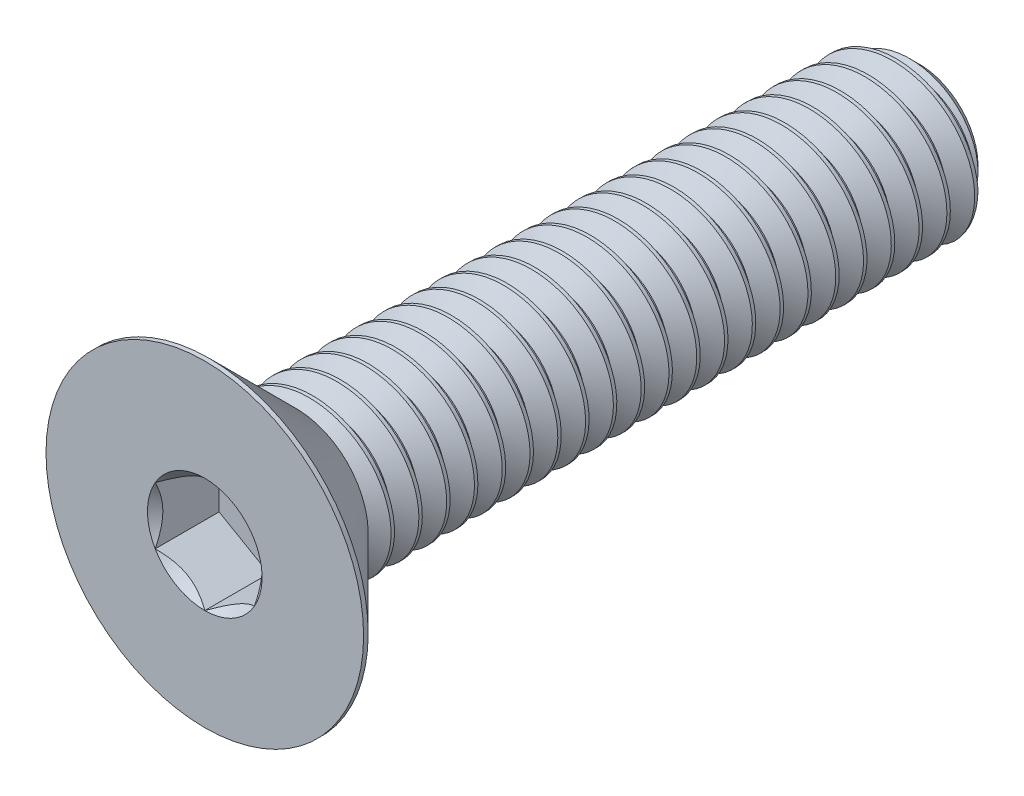
SolidWorks part; units mm, degrees
ref_plane "Front" through (0, 0, 0) normal (0, 0, 1) x (1, 0, 0)
ref_plane "Top" through (0, 0, 0) normal (0, 1, 0) x (1, 0, 0)
ref_plane "Right" through (0, 0, 0) normal (1, 0, 0) x (0, 0, -1)
sketch "Sketch11" plane through (0, 0, 0) normal (1, 0, 0) x (0, 0, -1)
  line L0 (-9, 4) -> (9, 4) construction
  line L5 (-9, 4) -> (-9, -4) construction
  line L6 (9, 2) -> (9, -2) construction
  line L7 (-8.99, 1.25) -> (-8.99, -1.25) construction
  line L8 (8.9562, 2.0758) -> (9.6562, 2.0758) construction
  line L9 (9.6562, 2.0758) -> (9.3062, 1.4696) construction
  line L10 (9.3062, 1.4696) -> (8.9562, 2.0758) construction
  line L11 (9.2625, 1.5453) -> (9.35, 1.5453) construction
  line L12 (9.3062, 1.5453) -> (9.3062, 1.4696) construction
  line L13 (8.9781, 2.0379) -> (9.6344, 2.0379) construction
  line L14 (9.3062, 2.0758) -> (9.3062, 2) construction
  line L15 (9, 2) -> (9.6125, 2) construction
  line L17 (-8.885, 4) -> (-4.885, 0) construction
  line L18 (-4.885, 0) -> (-8.885, -4) construction
  point P3 (-6.7, 4)
  point P8 (0, 4)
  point P21 (9.3062, 2.0379)
  point P26 (-9, 0)
  point P28 (-8.99, 0)
  point P29 (9, 0)
  dimension "Length" = 18
  dimension "Head Diameter" = 8
  dimension "Thread Major Diameter" = 4
  dimension "Head Height" = 2.3
  dimension "Drive Size" = 2.5
  dimension "Thread Pitch" = 0.7
  dimension "D1" = 0.0875
  dimension "D2" = 0.01
  dimension "D3" = 0.115
  dimension "Countersink Angle" = 90
sketch "Sketch1" plane through (0, 0, 0) normal (1, 0, 0) x (0, 0, -1)
  line L2 (-6.7, 2) -> (9, 2)
  line L3 (9, 2) -> (9, 0)
  line L4 (-7.39, 2) -> (-7.39, 0)
  line L5 (-6.7, 2) -> (-7.39, 2)
  line L6 (-9, 4) -> (-9, -4) construction
  line L7 (9, 2) -> (9, -2) construction
  line L8 (-7.39, 0) -> (9, 0)
  dimension "D1" = 1.61
revolve "Revolve1" add sketch "Sketch1" angle 360 mid plane about L8
chamfer "Chamfer1" distance 0.525 angle 45 1 edges at (0, -2, -9)
sketch "Sketch7" plane through (0, 0, 0) normal (1, 0, 0) x (0, 0, -1)
  line L2 (-9, 4) -> (-8.885, 4)
  line L5 (-6.7, 1.815) -> (-6.7, 0)
  line L6 (-9, 4) -> (-9, 0)
  line L8 (-9, 4) -> (-9, -4) construction
  line L9 (-9, 0) -> (-6.7, 0)
  line L12 (-8.885, 4) -> (-6.7, 1.815)
  line L13 (-8.885, 4) -> (-4.885, 0) construction
revolve "Revolve2" add sketch "Sketch7" angle 360 mid plane about L9 region at (0, 1.5544, 7.9977)
ref_plane "Plane1" through (0, 0, 6.7) normal (0, 0, 1) x (1, 0, 0)
sketch "Sketch5" plane through (0, 0, 9) normal (0, 0, 1) x (1, 0, 0)
  line L1 (1.25, -0.7217) -> (1.25, 0.7217)
  line L2 (1.25, 0.7217) -> (0, 1.4434)
  line L3 (0, 1.4434) -> (-1.25, 0.7217)
  line L4 (-1.25, 0.7217) -> (-1.25, -0.7217)
  line L5 (-1.25, -0.7217) -> (0, -1.4434)
  line L6 (0, -1.4434) -> (1.25, -0.7217)
  circle A0 centre (0, 0) radius 1.25 construction
extrude "Cut-Extrude2" cut sketch "Sketch5" against normal blind 1.61
sketch "Sketch6" plane through (0, 0, 9) normal (0, 0, -1) x (-1, 0, 0)
  circle A0 centre (0, 0) radius 1.4434
extrude "Cut-Extrude3" cut sketch "Sketch6" along normal blind 1.61 draft 45
sketch "Sketch12" plane through (0, 0, -9) normal (0, 0, -1) x (-1, 0, 0)
  circle A0 centre (0, 0) radius 2 construction
  circle A1 centre (0, 0) radius 2
curve "Helix/Spiral1" pitch 0.7 height 18 radius 2 centre (0, 0, -9) axis (0, 0, 1) start towards (0, 1, 0)
sketch "Sketch13" plane through (0, 0, 0) normal (1, 0, 0) x (0, 0, -1)
  line L0 (8.9781, 2.0379) -> (9.6344, 2.0379)
  line L1 (9.6344, 2.0379) -> (9.35, 1.5453)
  line L2 (9.35, 1.5453) -> (9.2625, 1.5453)
  line L3 (9.2625, 1.5453) -> (8.9781, 2.0379)
sweep "Cut-Sweep1" cut profiles "Sketch13" path "Helix/Spiral1" align with end faces yes
combine bodies "Combine1" operation type add bodies to combine 113 127
equation "\"D1@Chamfer1\"=\"Thread Pitch@Sketch11\" * .75"
equation "\"D1@Cut-Extrude2\"= \"Head Height@Sketch11\" * .7"
equation "\"D1@Cut-Extrude3\" = \"D1@Cut-Extrude2\""
equation "\"D1@Sketch11\"=\"Thread Pitch@Sketch11\"/8"
equation "\"D3@Sketch11\"=\"Head Height@Sketch11\"*.05"
equation "\"D4@Helix/Spiral1\"=\"Thread Pitch@Sketch11\""
equation "\"D1@Sketch1\"=\"Head Height@Sketch11\"*.7"
equation "\"D3@Helix/Spiral1\"=\"Length@Sketch11\""
